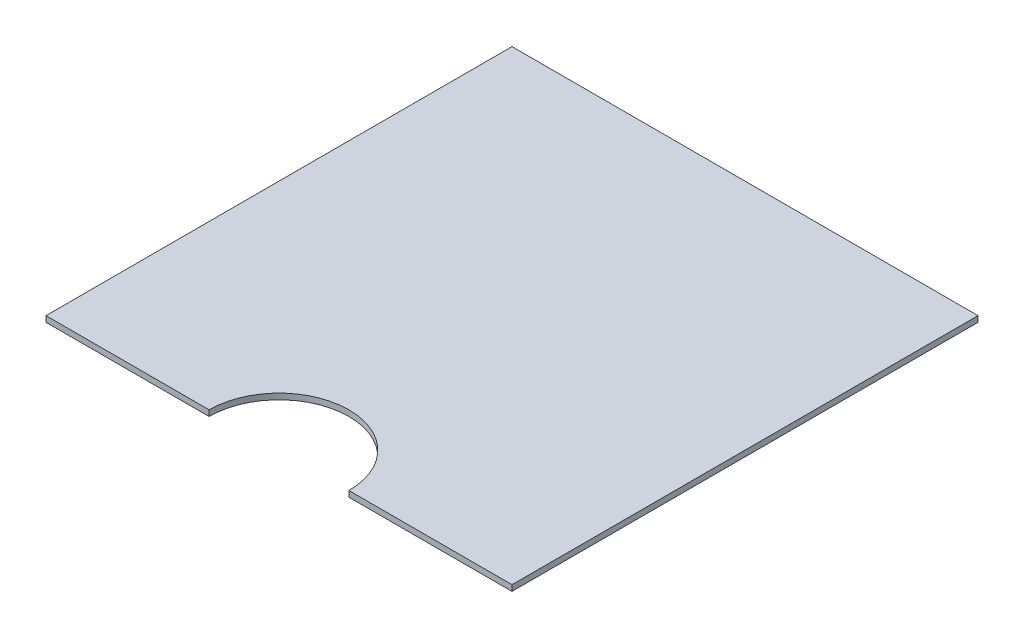
SolidWorks part; units mm, degrees
ref_plane "Front Plane" through (0, 0, 0) normal (0, 0, 1) x (1, 0, 0)
ref_plane "Top Plane" through (0, 0, 0) normal (0, 1, 0) x (1, 0, 0)
ref_plane "Right Plane" through (0, 0, 0) normal (1, 0, 0) x (0, 0, -1)
sketch "Sketch1" plane through (0, 0, 0) normal (0, 1, 0) x (1, 0, 0)
  line L1 (-200, -200) -> (200, -200)
  line L2 (-200, -200) -> (-200, 200)
  line L3 (-200, 200) -> (200, 200)
  line L4 (200, -200) -> (200, 200)
  line L5 (-200, -200) -> (200, 200) construction
  line L6 (-200, 200) -> (200, -200) construction
  point P0 (0, 0)
  dimension "D1" = 400
  dimension "D2" = 400
extrude "Boss-Extrude1" add sketch "Sketch1" along normal blind 5
sketch "Sketch2" plane through (0, 5, 0) normal (0, 1, 0) x (1, 0, 0)
  line L0 (-200, -200) -> (200, -200) construction
  line L1 (-60, -200) -> (60, -200)
  arc A0 (60, -200) -> (-60, -200) centre (0, -200) ccw
  dimension "D1" = 60
extrude "Cut-Extrude1" cut sketch "Sketch2" against normal blind 10
